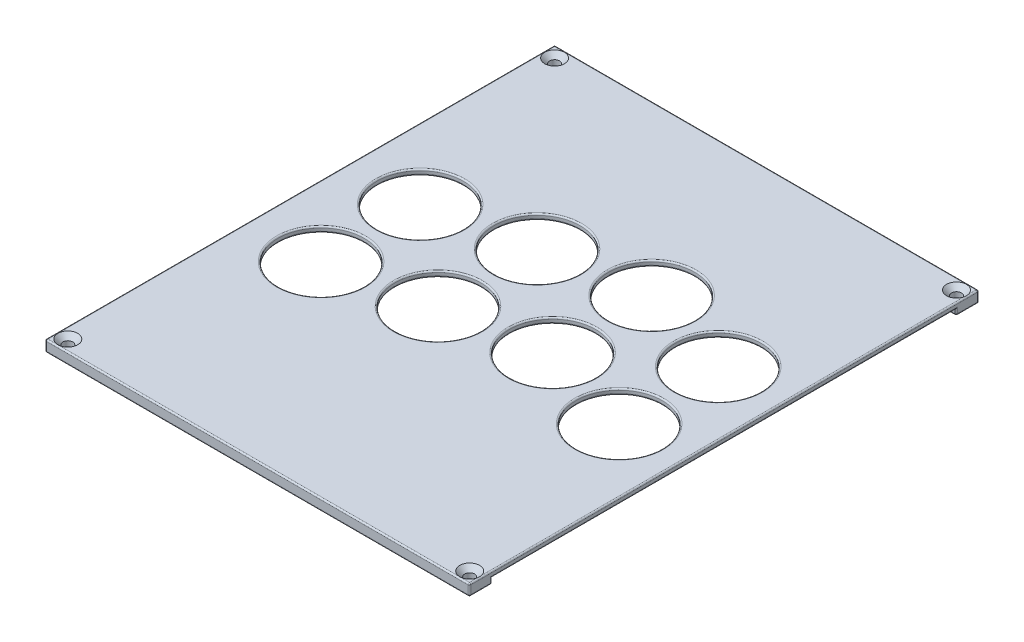
SolidWorks part; units mm, degrees
ref_plane "Front Plane" through (0, 0, 0) normal (0, 0, 1) x (1, 0, 0)
ref_plane "Top Plane" through (0, 0, 0) normal (0, 1, 0) x (1, 0, 0)
ref_plane "Right Plane" through (0, 0, 0) normal (1, 0, 0) x (0, 0, -1)
sketch "Sketch1" plane through (0, 0, 0) normal (0, 1, 0) x (1, 0, 0)
  line L0 (-125, -72.5) -> (-90.7071, -65.5) construction
  line L1 (0, 0) -> (-150, 0)
  line L2 (0, 0) -> (0, -180)
  line L3 (0, -180) -> (-150, -180)
  line L4 (-150, 0) -> (-150, -180)
  line L5 (-90.7071, -65.5) -> (-56.2253, -59.5) construction
  line L6 (-56.2253, -59.5) -> (-22.6842, -69.5) construction
  line L7 (-22.6842, -69.5) -> (-22.6842, -104.5) construction
  line L8 (-22.6842, -104.5) -> (-56.2253, -94.5) construction
  line L9 (-56.2253, -94.5) -> (-90.7071, -100.5) construction
  line L10 (-90.7071, -100.5) -> (-125, -107.5) construction
  line L11 (-125, -107.5) -> (-125, -72.5) construction
  line L12 (-90.7071, -100.5) -> (-90.7071, -65.5) construction
  line L13 (-56.2253, -94.5) -> (-56.2253, -59.5) construction
  line L14 (-22.6842, -69.5) -> (-22.6842, -59.5) construction
  line L15 (-22.6842, -59.5) -> (-56.2253, -59.5) construction
  line L16 (-56.2253, -59.5) -> (-90.7071, -59.5) construction
  line L17 (-90.7071, -65.5) -> (-90.7071, -59.5) construction
  line L18 (-90.7071, -65.5) -> (-125, -65.5) construction
  line L19 (-125, -65.5) -> (-125, -72.5) construction
  line L20 (-125, -72.5) -> (-150, -72.5) construction
  line L21 (-125, -72.5) -> (-125, 0) construction
  line L22 (-22.6842, -69.5) -> (0, -69.5) construction
  line L23 (-75, -145) -> (-150, -145) construction
  line L24 (-150, -172) -> (-142, -172) construction
  line L25 (-142, -172) -> (-142, -180) construction
  line L26 (-8, -180) -> (-8, -172) construction
  line L27 (-8, -172) -> (0, -172) construction
  line L28 (0, -8) -> (-8, -8) construction
  line L29 (-8, -8) -> (-8, 0) construction
  line L30 (-142, 0) -> (-142, -8) construction
  line L31 (-142, -8) -> (-150, -8) construction
  line L32 (-142, -8) -> (-150, 0) construction
  line L33 (-8, -8) -> (0, 0) construction
  line L34 (-8, -172) -> (0, -180) construction
  line L35 (-150, -180) -> (-142, -172) construction
  line L36 (-125, -107.5) -> (-125, -180) construction
  line L37 (-47.5, -162) -> (-102.5, -162) construction
  line L38 (-47.5, -162) -> (-47.5, -128) construction
  line L39 (-47.5, -128) -> (-102.5, -128) construction
  line L40 (-102.5, -162) -> (-102.5, -128) construction
  line L41 (-47.5, -162) -> (-102.5, -128) construction
  line L42 (-47.5, -128) -> (-102.5, -162) construction
  line L43 (-75, -145) -> (0, -145) construction
  line L44 (-75, -145) -> (-75, -180) construction
  line L45 (-142, -2) -> (-8, -2)
  line L46 (-100.1329, -128) -> (-101.3164, -125.95)
  line L47 (-101.3164, -125.95) -> (-103.6836, -125.95)
  line L48 (-103.6836, -125.95) -> (-104.8671, -128)
  line L49 (-104.8671, -128) -> (-103.6836, -130.05)
  line L50 (-103.6836, -130.05) -> (-101.3164, -130.05)
  line L51 (-101.3164, -130.05) -> (-100.1329, -128)
  line L52 (-45.1329, -128) -> (-46.3164, -125.95)
  line L53 (-46.3164, -125.95) -> (-48.6836, -125.95)
  line L54 (-48.6836, -125.95) -> (-49.8671, -128)
  line L55 (-49.8671, -128) -> (-48.6836, -130.05)
  line L56 (-48.6836, -130.05) -> (-46.3164, -130.05)
  line L57 (-46.3164, -130.05) -> (-45.1329, -128)
  line L58 (-46.3164, -164.05) -> (-45.1329, -162)
  line L59 (-45.1329, -162) -> (-46.3164, -159.95)
  line L60 (-46.3164, -159.95) -> (-48.6836, -159.95)
  line L61 (-48.6836, -159.95) -> (-49.8671, -162)
  line L62 (-49.8671, -162) -> (-48.6836, -164.05)
  line L63 (-48.6836, -164.05) -> (-46.3164, -164.05)
  line L64 (-100.1329, -162) -> (-101.3164, -159.95)
  line L65 (-101.3164, -159.95) -> (-103.6836, -159.95)
  line L66 (-103.6836, -159.95) -> (-104.8671, -162)
  line L67 (-104.8671, -162) -> (-103.6836, -164.05)
  line L68 (-103.6836, -164.05) -> (-101.3164, -164.05)
  line L69 (-101.3164, -164.05) -> (-100.1329, -162)
  line L70 (-106, -166) -> (-44, -166)
  line L71 (-106, -166) -> (-106, -124)
  line L72 (-106, -124) -> (-44, -124)
  line L73 (-44, -166) -> (-44, -124)
  line L74 (-106, -166) -> (-44, -124) construction
  line L75 (-106, -124) -> (-44, -166) construction
  line L76 (-148, -8) -> (-148, -172)
  line L77 (-142, -178) -> (-8, -178)
  line L78 (-142, -2) -> (-142, -8)
  line L79 (-142, -8) -> (-148, -8)
  line L80 (-8, -2) -> (-8, -8)
  line L81 (-8, -8) -> (0, -8)
  line L82 (0, -172) -> (-8, -172)
  line L83 (-8, -172) -> (-8, -178)
  line L84 (-142, -178) -> (-142, -172)
  line L85 (-142, -172) -> (-148, -172)
  line L86 (-147.7, -90) -> (-147.7, -80)
  line L87 (-2.3, -2.3) -> (-147.7, -2.3) construction
  line L88 (-147.7, -2.3) -> (-147.7, -177.7) construction
  line L89 (-2.3, -177.7) -> (-147.7, -177.7) construction
  line L90 (-2.3, -2.3) -> (-2.3, -177.7) construction
  line L91 (-75, -2.3) -> (-65, -2.3)
  line L92 (-65, -2.3) -> (-65, -4.3)
  line L93 (-65, -4.3) -> (-85, -4.3)
  line L94 (-85, -4.3) -> (-85, -2.3)
  line L95 (-85, -2.3) -> (-75, -2.3)
  line L96 (-147.7, -80) -> (-145.7, -80)
  line L97 (-145.7, -80) -> (-145.7, -100)
  line L98 (-145.7, -100) -> (-147.7, -100)
  line L99 (-147.7, -100) -> (-147.7, -90)
  line L100 (-75, -177.7) -> (-65, -177.7)
  line L101 (-65, -177.7) -> (-65, -175.7)
  line L102 (-65, -175.7) -> (-85, -175.7)
  line L103 (-85, -175.7) -> (-85, -177.7)
  line L104 (-85, -177.7) -> (-75, -177.7)
  circle A16 centre (-125, -72.5) radius 15 construction
  circle A17 centre (-90.7071, -65.5) radius 15 construction
  circle A18 centre (-56.2253, -59.5) radius 15 construction
  circle A19 centre (-22.6842, -69.5) radius 15 construction
  circle A20 centre (-125, -107.5) radius 15 construction
  circle A21 centre (-90.7071, -100.5) radius 15 construction
  circle A22 centre (-56.2253, -94.5) radius 15 construction
  circle A23 centre (-22.6842, -104.5) radius 15 construction
  circle A24 centre (-125, -72.5) radius 15.2
  circle A25 centre (-90.7071, -65.5) radius 15.2
  circle A26 centre (-56.2253, -59.5) radius 15.2
  circle A27 centre (-22.6842, -69.5) radius 15.2
  circle A28 centre (-22.6842, -104.5) radius 15.2
  circle A29 centre (-56.2253, -94.5) radius 15.2
  circle A30 centre (-90.7071, -100.5) radius 15.2
  circle A31 centre (-125, -107.5) radius 15.2
  circle A32 centre (-146, -4) radius 1.75
  circle A33 centre (-4, -4) radius 1.75
  circle A34 centre (-4, -176) radius 1.75
  circle A35 centre (-146, -176) radius 1.75
  circle A36 centre (-102.5, -128) radius 2.05 construction
  circle A37 centre (-47.5, -128) radius 2.05 construction
  circle A38 centre (-47.5, -162) radius 2.05 construction
  circle A39 centre (-102.5, -162) radius 2.05 construction
  point P23 (-75, -145)
  dimension "D1" = 30
  dimension "D7" = 3.5
  dimension "D14" = 4.1
  dimension "D22" = 2.3
  dimension "D3" = 10
  dimension "D4" = 6
  dimension "D5" = 7
  dimension "D6" = 8
  dimension "D8" = 0.2
  dimension "D2" = 35
  dimension "D9" = 180
  dimension "D10" = 150
  dimension "D11" = 55
  dimension "D12" = 34
  dimension "D13" = 35
  dimension "D15" = 42
  dimension "D16" = 62
  dimension "D17" = 2
  dimension "D18" = 2
  dimension "D19" = 2
  dimension "D20" = 25
  dimension "D21" = 2
  dimension "D23" = 2
  dimension "D24" = 20
  dimension "D25" = 20
  dimension "D26" = 2
  dimension "D27" = 20
extrude "Boss-Extrude1" add sketch "Sketch1" along normal blind 2 contours L1 L4 L3 L2 A35 A34 A33 A32 A31 A30 A29 A28 A27 A26 A25 A24 L73 L70 L71 L72 | L70 L73 L72 L71 L51 L50 L49 L48 L47 L46 L57 L56 L55 L54 L53 L52 L63 L62 L61 L60 L59 L58 L69 L68 L67 L66 L65 L64 | L68 L69 L64 L65 L66 L67 | L84 L85 L76 L79 L78 L45 L80 L81 L2 L1 L4 L3 L82 L83 L77 A35 A34 A33 A32 | L48 L49 L50 L51 L46 L47 | L52 L53 L54 L55 L56 L57 | L58 L59 L60 L61 L62 L63 | L102 L103 L104 L100 L101 | L97 L98 L99 L86 L96 | L93 L94 L95 L91 L92 region at (-0.2343, 0, 4) region at (-73.8861, 0, 83.6694) region at (-102.5, 0, 162) region at (-75, 0, 145)
extrude "Boss-Extrude2" add sketch "Sketch1<4>" against normal blind 2 contours L84 L85 L76 L79 L78 L45 L80 L81 L2 L1 L4 L3 L82 L83 L77 A35 A34 A33 A32 region at (-0.2343, 0, 4)
sketch "Sketch1<4>" plane through (0, 0, 0) normal (0, 1, 0) x (1, 0, 0) same geometry as "Sketch1"
extrude "Boss-Extrude3" add sketch "Sketch1<5>" against normal blind 4 contours L102 L103 L104 L100 L101 | L97 L98 L99 L86 L96 | L93 L94 L95 L91 L92
sketch "Sketch1<5>" plane through (0, 0, 0) normal (0, 1, 0) x (1, 0, 0) same geometry as "Sketch1"
sketch "Sketch2" plane through (0, 0, 0) normal (1, 0, 0) x (0, 0, -1)
  line L9 (-180, 2) -> (0, 2)
  line L13 (0, 2) -> (0, -2)
  line L14 (0, -2) -> (-8, -2) construction
  line L15 (0, -2) -> (-8, -2)
  line L16 (-8, -2) -> (-8, 0)
  line L17 (-8, 0) -> (-172, 0)
  line L18 (-172, 0) -> (-172, -2)
  line L19 (-172, -2) -> (-180, -2)
  line L22 (-180, -2) -> (-180, 2)
  line M2 (0, -2) -> (0, 2)
  line M4 (-180, 2) -> (-180, -2)
  line M9 (-172, 0) -> (-8, 0)
  line M10 (0, 2) -> (-180, 2)
  line M24 (-8, 0) -> (-8, -2)
  line M25 (-8, -2) -> (0, -2)
  line M26 (-180, -2) -> (-172, -2)
  line M27 (-172, -2) -> (-172, 0)
extrude "Cut-Extrude1" cut sketch "Sketch2" against normal blind 0.1 contours M27 M9 M24 M25 M2 M10 M4 M26 region at (0, 0.8367, 90)
fillet "Fillet1" radius 0.5 63 edges at (-150, 0, 0) (-150, 0, 180) (-75.05, 2, 0) (-0.1, 0, 0) (-150, 2, 90) (-75.05, 2, 180) (-0.1, 0, 180) (-22.6842, 0, 119.7) (-22.6842, 2, 119.7) (-22.6842, 0, 84.7) (-22.6842, 2, 84.7) (-56.2253, 0, 74.7) (-56.2253, 2, 74.7) (-56.2253, 0, 109.7) (-56.2253, 2, 109.7) (-90.7071, 0, 115.7) (-90.7071, 2, 115.7) (-90.7071, 0, 80.7) (-90.7071, 2, 80.7) (-125, 0, 87.7) (-125, 2, 87.7) (-125, 0, 122.7) (-125, 2, 122.7) (-0.1, 2, 90) (-0.1, 0, 90) (-75.05, -2, 0) (-150, -2, 90) (-75.05, -2, 180) (-0.1, -2, 176) (-0.1, -2, 4) (-0.1, -1, 8) (-0.1, -1, 172) (-8, -1, 8) (-4.05, -2, 172) (-8, -2, 175) (-75, -2, 178) (-142, -2, 175) (-145, -2, 172) (-148, -2, 90) (-145, -2, 8) (-142, -2, 5) (-75, -2, 2) (-8, -2, 5) (-4.05, -2, 8) (-146, -2, 5.75) (-4, -2, 5.75) (-4, -2, 177.75) (-146, -2, 177.75) (-142, -1, 8) (-142, -1, 172) (-8, -1, 172) (-75, -4, 175.7) (-85, -4, 176.7) (-75, -4, 177.7) (-65, -4, 176.7) (-147.7, -4, 90) (-146.7, -4, 100) (-145.7, -4, 90) (-146.7, -4, 80) (-75, -4, 2.3) (-85, -4, 3.3) (-75, -4, 4.3) (-65, -4, 3.3)
chamfer "Chamfer1" distance 1.75 angle 45 4 edges at (-146, 2, 177.75) (-4, 2, 177.75) (-4, 2, 5.75) (-146, 2, 5.75)
